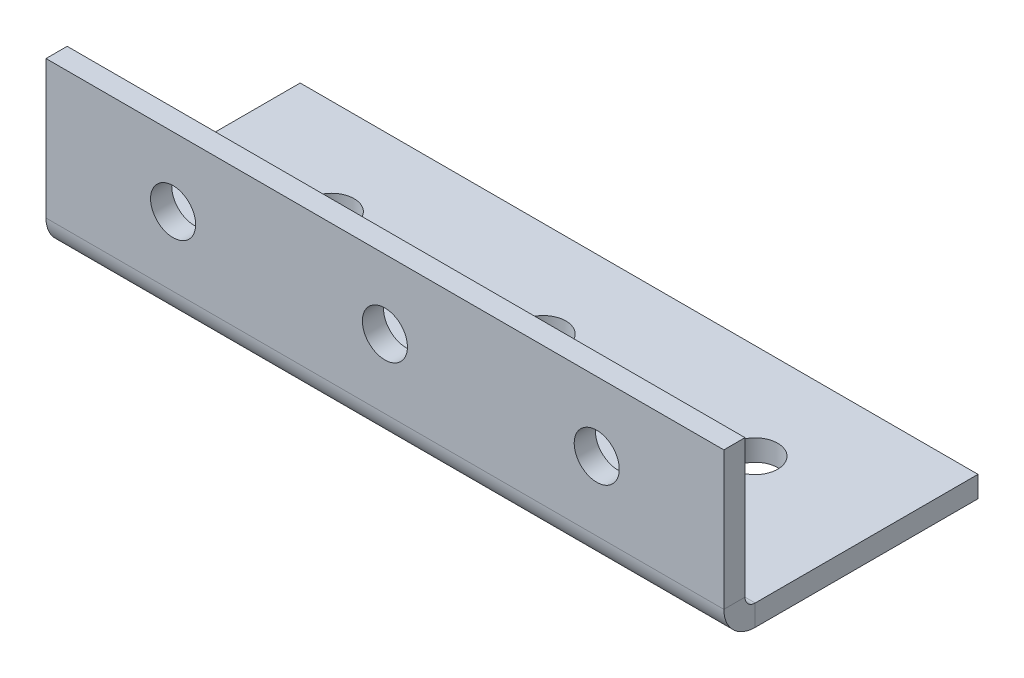
SolidWorks part; units mm, degrees
note: The reader was unsure of these and kept them because the rebuilt part matched: flange length of "Edge-Flange1".
material "6061-T6 (SS)"
ref_plane "Front" through (0, 0, 0) normal (0, 0, 1) x (1, 0, 0)
ref_plane "Top" through (0, 0, 0) normal (0, 1, 0) x (1, 0, 0)
ref_plane "Right" through (0, 0, 0) normal (1, 0, 0) x (0, 0, -1)
sketch "Sketch1" plane through (0, 0, 0) normal (0, 1, 0) x (1, 0, 0)
  line L1 (0, 0) -> (101.6, 0)
  line L2 (0, 0) -> (0, 38.1)
  line L3 (0, 38.1) -> (101.6, 38.1)
  line L4 (101.6, 0) -> (101.6, 38.1)
  dimension "D1" = 101.6
  dimension "D2" = 38.1
base flange "Base-Flange1" sketch "Sketch1" thickness 3.175 reverse thickness direction no parameters "D1"=1.524
edge flange "Edge-Flange1" sketch "Sketch8" flange angle 90 flange length 25.4 flange position material inside bend radius 1.524 thickness 3.175 relief rectangular parameters "D6"=10
sketch "Sketch8" plane through (0, 0, 0) normal (0, 0, 1) x (1, 0, 0)
  line L2 (0, 0) -> (0, 22.225)
  line L3 (0, 22.225) -> (101.6, 22.225)
  line L4 (101.6, 22.225) -> (101.6, 0)
  line L7 (0, 0) -> (101.6, 0) construction
  line L8 (0, 0) -> (101.6, 0)
bend "EdgeBend1" bend radius 1.524 bend angle 90 parameters "D5"=1
hole_wizard "1/4 Clearance Hole1" positions "3DSketch1" profile "Sketch9" hole size "1/4" standard "ANSI Inch" end condition up to next
sketch3d "3DSketch1"
  line L5 (19.05, 11.8745, -3.175) -> (0, 11.8745, -3.175) construction
  line L6 (0, 22.225, -3.175) -> (0, 1.524, -3.175) construction
  line L8 (82.55, 11.8745, -3.175) -> (101.6, 11.8745, -3.175) construction
  line L9 (101.6, 1.524, -3.175) -> (101.6, 22.225, -3.175) construction
  line L11 (101.6, 0, -4.699) -> (0, 0, -4.699) construction
  line L13 (0, 0, -38.1) -> (0, 0, -4.699) construction
  point P0 (19.05, 0, -23.749)
  point P2 (50.8, 0, -23.749)
  point P4 (82.55, 0, -23.749)
  point P6 (19.05, 11.8745, -3.175)
  point P8 (50.8, 11.8745, -3.175)
  point P10 (82.55, 11.8745, -3.175)
  dimension "D1" = 31.75
  dimension "D2" = 31.75
  dimension "D3" = 19.05
  dimension "D4" = 31.75
  dimension "D5" = 31.75
  dimension "D6" = 19.05
sketch "Sketch9" plane through (19.05, 0, -23.749) normal (1, 0, 0) x (0, 0, 1)
  line L0 (0, 0) -> (0, 3.175)
  line L1 (0, 3.175) -> (3.3782, 3.175)
  line L2 (3.3782, 3.175) -> (3.3782, 0)
  line L5 (3.3782, 0) -> (0, 0)
  line L11 (0, -6.35) -> (0, 107.95) construction
  dimension "Thru Hole Dia." = 6.7564
  dimension "Thru Hole Depth" = 3.175
sketch "Bend-Lines1" [suppressed] plane through (0, 0, 0) normal (0, 1, 0) x (1, 0, 0)
sketch "Bounding-Box1" [suppressed] plane through (0, 0, 0) normal (0, 1, 0) x (1, 0, 0)
sheet metal parameters "Sheet-Metal8" thickness 3.175 parameters "D1"=1.524
flat pattern "Flat-Pattern8" [suppressed]
sketch "Bend-Lines2" plane through (0, 0, 0) normal (0, 1, 0) x (1, 0, 0)
sketch "Bounding-Box2" [suppressed] plane through (0, 0, 0) normal (0, 1, 0) x (1, 0, 0)
sheet metal parameters "Sheet-Metal9" thickness 3.175 parameters "D1"=1.524
flat pattern "Flat-Pattern8"
sketch "Bend-Lines2" plane through (0, 0, 0) normal (0, 1, 0) x (1, 0, 0)
  line L0 (0, 2.2552) -> (101.6, 2.2552) construction
  line L1 (0, 2.2552) -> (101.6, 2.2552) construction
sketch3d "Bounding-Box2" [suppressed]
  line L0 (101.6, 38.1, 0) -> (0, 38.1, 0) construction
  line L1 (101.6, -20.8895, 0) -> (0, -20.8895, 0) construction
  line L2 (101.6, 38.1, 0) -> (101.6, -20.8895, 0) construction
  line L3 (0, 38.1, 0) -> (0, -20.8895, 0) construction
bend of the flat pattern "Flatten-<EdgeBend1>1"
sheet metal parameters "Sheet-Metal10" thickness 3.175 parameters "D1"=1.524
flat pattern "Flat-Pattern8"
sketch "Bend-Lines2" plane through (0, 0, 0) normal (0, 1, 0) x (1, 0, 0)
  line L0 (0, 2.2552) -> (101.6, 2.2552) construction
  line L1 (0, 2.2552) -> (101.6, 2.2552) construction
sketch3d "Bounding-Box2" [suppressed]
  line L0 (101.6, 38.1, 0) -> (0, 38.1, 0) construction
  line L1 (101.6, -20.8895, 0) -> (0, -20.8895, 0) construction
  line L2 (101.6, 38.1, 0) -> (101.6, -20.8895, 0) construction
  line L3 (0, 38.1, 0) -> (0, -20.8895, 0) construction
bend of the flat pattern "Flatten-<EdgeBend1>1"
